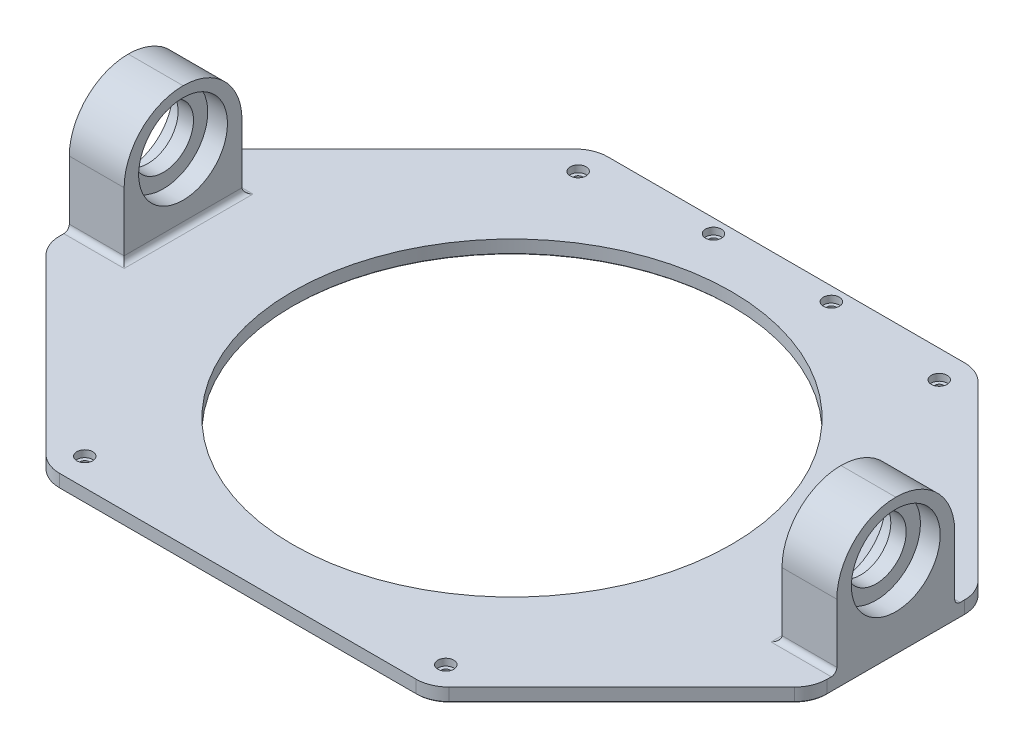
SolidWorks part; units mm, degrees
ref_plane "前视基准面" through (0, 0, 0) normal (0, 0, 1) x (1, 0, 0)
ref_plane "上视基准面" through (0, 0, 0) normal (0, 1, 0) x (1, 0, 0)
ref_plane "右视基准面" through (0, 0, 0) normal (1, 0, 0) x (0, 0, -1)
other "Configuration Table"
sketch "草图1" plane through (0, 0, 0) normal (0, 1, 0) x (1, 0, 0)
  line L1 (0, 0) -> (280, 0)
  line L2 (0, 0) -> (0, -280)
  line L3 (0, -280) -> (280, -280)
  line L4 (280, 0) -> (280, -280)
  dimension "D1" = 280
  dimension "D2" = 280
extrude "凸台-拉伸1" add sketch "草图1" along normal blind 5
sketch "草图2" plane through (0, 5, 0) normal (0, 1, 0) x (1, 0, 0)
  line L0 (0, -280) -> (280, -280) construction
  circle A0 centre (140, -180) radius 80
  point P4 (140, -280)
  dimension "D1" = 160
  dimension "D2" = 0
  dimension "D3" = 100
extrude "切除-拉伸1" cut sketch "草图2" against normal blind 5
sketch "草图3" plane through (0, 5, 0) normal (0, 1, 0) x (1, 0, 0)
  line L0 (0, 0) -> (0, -280) construction
  line L1 (0, -158.5) -> (20, -158.5)
  line L2 (0, -158.5) -> (0, -201.5)
  line L3 (0, -201.5) -> (20, -201.5)
  line L4 (20, -158.5) -> (20, -201.5)
  line L5 (280, -280) -> (280, 0) construction
  line L6 (280, -158.5) -> (260, -158.5)
  line L7 (280, -158.5) -> (280, -201.5)
  line L8 (280, -201.5) -> (260, -201.5)
  line L9 (260, -158.5) -> (260, -201.5)
  circle A0 centre (140, -180) radius 80 construction
  point P12 (20, -180)
  point P15 (260, -180)
  dimension "D1" = 0
  dimension "D2" = 0
  dimension "D3" = 43
  dimension "D4" = 43
  dimension "D5" = 20
  dimension "D6" = 20
extrude "凸台-拉伸2" add sketch "草图3" along normal blind 45
sketch "草图4" plane through (280, 0, 0) normal (1, 0, 0) x (0, 0, -1)
  line L0 (-201.5, 50) -> (-158.5, 50) construction
  circle A0 centre (-180, 30) radius 11
  point P4 (-180, 50)
  dimension "D1" = 0
  dimension "12.5" = 22
  dimension "D2" = 20
extrude "切除-拉伸2" cut sketch "草图4" against normal through all
sketch "草图5" plane through (280, 0, 0) normal (1, 0, 0) x (0, 0, -1)
  circle A0 centre (-180, 30) radius 16.2
  dimension "D1" = 32.4
extrude "切除-拉伸3" cut sketch "草图5" against normal blind 7.2
sketch "草图6" plane through (260, 0, 0) normal (-1, 0, 0) x (0, 0, 1)
  circle A0 centre (180, 30) radius 16.2
  dimension "D1" = 32.4
extrude "切除-拉伸4" cut sketch "草图6" against normal blind 7.2
sketch "草图7" plane through (20, 0, 0) normal (1, 0, 0) x (0, 0, -1)
  circle A0 centre (-180, 30) radius 16.2
  dimension "D1" = 32.4
extrude "切除-拉伸5" cut sketch "草图7" against normal blind 7.2
sketch "草图8" plane through (0, 0, 0) normal (-1, 0, 0) x (0, 0, 1)
  circle A0 centre (180, 30) radius 16.2
  dimension "D1" = 32.4
extrude "切除-拉伸6" cut sketch "草图8" against normal blind 7.2
sketch "草图9" plane through (0, 5, 0) normal (0, 1, 0) x (1, 0, 0)
  line L0 (280, -158.5) -> (280, 0) construction
  line L1 (0, 0) -> (280, 0)
  line L2 (0, 0) -> (0, -80)
  line L3 (0, -80) -> (280, -80)
  line L4 (280, 0) -> (280, -80)
  circle A0 centre (140, -180) radius 80 construction
  dimension "D1" = 100
extrude "切除-拉伸7" cut sketch "草图9" against normal through all
chamfer "倒角1" distance 70 angle 45 4 edges at (280, 2.5, 80) (280, 2.5, 280) (0, 2.5, 280) (0, 2.5, 80)
fillet "圆角1" radius 21.5 4 edges at (270, 50, 201.5) (270, 50, 158.5) (10, 50, 201.5) (10, 50, 158.5)
fillet "圆角2" radius 12 8 edges at (70, 2.5, 80) (210, 2.5, 80) (280, 2.5, 150) (280, 2.5, 210) (210, 2.5, 280) (70, 2.5, 280) (0, 2.5, 210) (0, 2.5, 150)
fillet "圆角3" radius 2 6 edges at (260, 5, 180) (270, 5, 201.5) (270, 5, 158.5) (10, 5, 158.5) (20, 5, 180) (10, 5, 201.5)
sketch "草图10" plane through (0, 0, 0) normal (0, -1, 0) x (-1, 0, 0)
  line L1 (-140, -80) -> (-140, -118.5005) construction
  line L3 (0, -154.9706) -> (0, -205.0294) construction
  line L4 (-74.9706, -80) -> (-205.0294, -80) construction
  circle A0 centre (-20, -187.5) radius 1.6
  circle A1 centre (-20, -172.5) radius 1.6
  circle A5 centre (-260, -187.5) radius 1.6
  circle A6 centre (-260, -172.5) radius 1.6
  circle A7 centre (-140, -180) radius 80 construction
  dimension "D1" = 3.2
  dimension "D2" = 3.2
  dimension "D4" = 20
  dimension "D5" = 15
  dimension "D6" = 7.5
  dimension "D3" = 20
extrude "切除-拉伸8" cut sketch "草图10" against normal blind 5
sketch "草图11" plane through (0, 0, 0) normal (0, -1, 0) x (-1, 0, 0)
  circle A4 centre (-20, -172.5) radius 2.35
  circle A5 centre (-20, -187.5) radius 2.35
  circle A6 centre (-260, -172.5) radius 2.35
  circle A7 centre (-260, -187.5) radius 2.35
  dimension "D1" = 4.7
  dimension "D2" = 4.7
  dimension "D3" = 4.7
  dimension "D4" = 4.7
extrude "切除-拉伸9" cut sketch "草图11" against normal blind 4.2
sketch "草图12" plane through (0, 5, 0) normal (0, 1, 0) x (1, 0, 0)
  circle A0 centre (118.5, -85) radius 1.65
  circle A1 centre (161.5, -85) radius 1.65
  circle A3 centre (140, -180) radius 80 construction
  dimension "D1" = 43
  dimension "D2" = 21.5
  dimension "D3" = 95
  dimension "D4" = 95
  dimension "D5" = 3.3
  dimension "D6" = 3.3
extrude "切除-拉伸10" cut sketch "草图12" against normal blind 10
sketch "草图13" plane through (0, 5, 0) normal (0, 1, 0) x (1, 0, 0)
  circle A0 centre (118.5, -85) radius 2.9
  circle A1 centre (161.5, -85) radius 2.9
  dimension "D1" = 5.8
  dimension "D2" = 5.8
extrude "切除-拉伸11" cut sketch "草图13" against normal blind 2.5
sketch "草图14" plane through (0, 5, 0) normal (0, 1, 0) x (1, 0, 0)
  line L0 (74.9706, -80) -> (205.0294, -80) construction
  line L1 (66.4853, -83.5147) -> (3.5147, -146.4853) construction
  line L2 (276.4853, -146.4853) -> (213.5147, -83.5147) construction
  line L3 (3.5147, -213.5147) -> (66.4853, -276.4853) construction
  line L4 (74.9706, -280) -> (205.0294, -280) construction
  line L5 (213.5147, -276.4853) -> (276.4853, -213.5147) construction
  circle A0 centre (74.1421, -90) radius 1.6
  circle A1 centre (74.1421, -270) radius 1.6
  circle A2 centre (205.8579, -270) radius 1.6
  circle A3 centre (205.8579, -90) radius 1.6
  dimension "D1" = 3.2
  dimension "D2" = 10
  dimension "D3" = 10
  dimension "D4" = 3.2
  dimension "D5" = 3.2
  dimension "D6" = 3.2
  dimension "D7" = 10
  dimension "D9" = 10
  dimension "D10" = 10
  dimension "D11" = 10
  dimension "D12" = 10
  dimension "D8" = 10
extrude "切除-拉伸12" cut sketch "草图14" against normal blind 10
sketch "草图15" plane through (0, 5, 0) normal (0, 1, 0) x (1, 0, 0)
  circle A0 centre (74.1421, -270) radius 2.9
  circle A1 centre (205.8579, -270) radius 2.9
  circle A2 centre (205.8579, -90) radius 2.9
  circle A3 centre (74.1421, -90) radius 2.9
  dimension "D1" = 5.8
  dimension "D2" = 5.8
  dimension "D3" = 5.8
  dimension "D4" = 5.8
extrude "切除-拉伸13" cut sketch "草图15" against normal blind 2.5
chamfer "倒角4" distance 0.4 angle 45 27 edges at (0.9134, 0, 150.3784) (0, 0, 180) (0.9134, 0, 209.6216) (35, 0, 245) (70.3784, 0, 279.0866) (140, 0, 280) (209.6216, 0, 279.0866) (245, 0, 245) (279.0866, 0, 209.6216) (280, 0, 180) (279.0866, 0, 150.3784) (245, 0, 115) (209.6216, 0, 80.9134) (140, 0, 80) (70.3784, 0, 80.9134) (35, 0, 115) (140, 0, 260) (20, 0, 170.15) (260, 0, 185.15) (260, 0, 170.15) (20, 0, 185.15) (161.5, 0, 86.65) (118.5, 0, 86.65) (74.1421, 0, 91.6) (74.1421, 0, 271.6) (205.8579, 0, 271.6) (205.8579, 0, 91.6)
